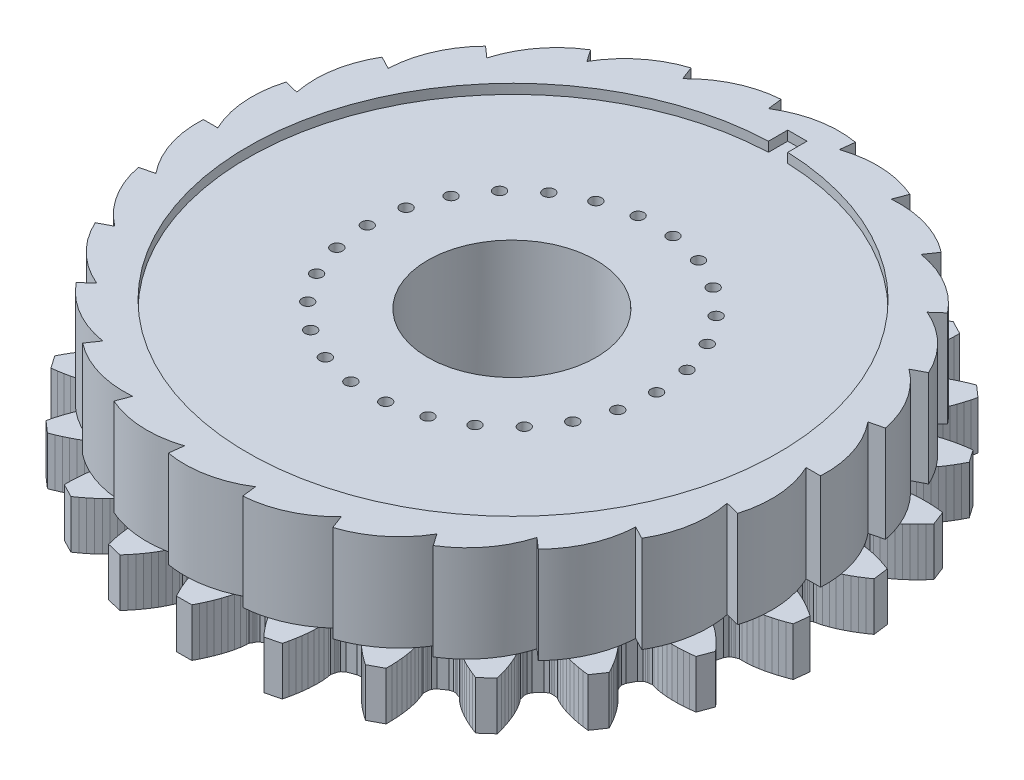
SolidWorks part; units mm, degrees
material "1060 Alloy"
ref_plane "Front Plane" through (0, 0, 0) normal (0, 0, 1) x (1, 0, 0)
ref_plane "Top Plane" through (0, 0, 0) normal (0, 1, 0) x (1, 0, 0)
ref_plane "Right Plane" through (0, 0, 0) normal (1, 0, 0) x (0, 0, -1)
sketch "Sketch1" plane through (0, 0, 0) normal (0, 1, 0) x (1, 0, 0)
  line L0 (0, 0) -> (54.8903, 0) construction
  line L1 (0, 0) -> (47.5263, 11.7142) construction
  line L2 (0, 0) -> (29.6137, 7.2991)
  line L3 (0, 0) -> (32, 0)
  circle A0 centre (0, 0) radius 32 construction
  circle A1 centre (0, 0) radius 30.5 construction
  arc A2 (29.6137, 7.2991) -> (32, 0) centre (21.3514, 0.5583) cw
  circle A3 centre (0, 0) radius 31.25 construction
  dimension "D1" = 62.5
  dimension "D2" = 1.5
  dimension "D4" = 0.75
  dimension "D3" = 13.846
extrude "Extrude ratchet edge" add sketch "Sketch1" along normal blind 10
pattern_circular "Pattern edge to form gear" count 26 over 360 about axis through (0, 10, 0) along (0, -1, 0) of "Extrude ratchet edge" reverse direction yes
sketch "Sketch7" plane through (0, 10, 0) normal (0, 1, 0) x (1, 0, 0)
  circle A0 centre (0, 0) radius 8.7313
  dimension "D1" = 17.4625
sketch "Sketch12" plane through (0, 0, 0) normal (0, -1, 0) x (1, 0, 0)
  line L0 (29.0003, -0.6166) -> (29.1196, -1.0003)
  line L1 (29.1196, -1.0003) -> (29.244, -1.1506)
  line L2 (29.244, -1.1506) -> (29.3694, -1.2597)
  line L3 (29.3694, -1.2597) -> (29.4955, -1.346)
  line L4 (29.4955, -1.346) -> (29.7463, -1.5351)
  line L5 (29.7463, -1.5351) -> (30.0039, -1.5796)
  line L6 (30.0039, -1.5796) -> (30.5166, -1.7122)
  line L7 (30.5166, -1.7122) -> (31.0266, -1.8861)
  line L8 (31.0266, -1.8861) -> (31.5336, -2.0936)
  line L9 (31.5336, -2.0936) -> (32.0376, -2.3308)
  line L10 (32.0376, -2.3308) -> (32.5381, -2.595)
  line L11 (32.5381, -2.595) -> (33.035, -2.8848)
  line L12 (33.035, -2.8848) -> (33.5277, -3.1987)
  line L13 (33.5277, -3.1987) -> (34.0159, -3.5359)
  line L14 (34.0159, -3.5359) -> (33.8164, -5.1042)
  line L15 (33.8164, -5.1042) -> (33.2594, -5.3084)
  line L16 (33.2594, -5.3084) -> (32.7038, -5.4891)
  line L17 (32.7038, -5.4891) -> (32.1503, -5.6453)
  line L18 (32.1503, -5.6453) -> (31.5995, -5.7759)
  line L19 (31.5995, -5.7759) -> (31.0523, -5.8793)
  line L20 (31.0523, -5.8793) -> (30.5094, -5.9534)
  line L21 (30.5094, -5.9534) -> (29.9722, -5.9942)
  line L22 (29.9722, -5.9942) -> (29.4426, -5.9942)
  line L23 (29.4426, -5.9942) -> (29.182, -5.9728)
  line L24 (29.182, -5.9728) -> (28.8919, -6.0931)
  line L25 (28.8919, -6.0931) -> (28.7482, -6.1452)
  line L26 (28.7482, -6.1452) -> (28.5995, -6.2194)
  line L27 (28.5995, -6.2194) -> (28.4414, -6.3338)
  line L28 (28.4414, -6.3338) -> (28.2299, -6.6755)
  line L29 (28.2299, -6.6755) -> (28.0119, -7.539)
  line L30 (28.0119, -7.539) -> (28.0359, -7.9401)
  line L31 (28.0359, -7.9401) -> (28.1207, -8.1159)
  line L32 (28.1207, -8.1159) -> (28.2164, -8.2517)
  line L33 (28.2164, -8.2517) -> (28.3182, -8.3658)
  line L34 (28.3182, -8.3658) -> (28.5164, -8.6094)
  line L35 (28.5164, -8.6094) -> (28.7559, -8.7142)
  line L36 (28.7559, -8.7142) -> (29.222, -8.9657)
  line L37 (29.222, -8.9657) -> (29.6755, -9.2566)
  line L38 (29.6755, -9.2566) -> (30.1181, -9.5794)
  line L39 (30.1181, -9.5794) -> (30.5507, -9.9303)
  line L40 (30.5507, -9.9303) -> (30.9735, -10.3067)
  line L41 (30.9735, -10.3067) -> (31.3865, -10.7069)
  line L42 (31.3865, -10.7069) -> (31.7898, -11.1296)
  line L43 (31.7898, -11.1296) -> (32.1831, -11.5738)
  line L44 (32.1831, -11.5738) -> (31.6141, -13.0488)
  line L45 (31.6141, -13.0488) -> (31.0244, -13.1138)
  line L46 (31.0244, -13.1138) -> (30.4418, -13.1563)
  line L47 (30.4418, -13.1563) -> (29.8669, -13.1754)
  line L48 (29.8669, -13.1754) -> (29.3009, -13.1704)
  line L49 (29.3009, -13.1704) -> (28.7448, -13.1399)
  line L50 (28.7448, -13.1399) -> (28.2, -13.0819)
  line L51 (28.2, -13.0819) -> (27.6686, -12.9929)
  line L52 (27.6686, -12.9929) -> (27.1544, -12.8663)
  line L53 (27.1544, -12.8663) -> (26.9065, -12.7831)
  line L54 (26.9065, -12.7831) -> (26.5961, -12.8305)
  line L55 (26.5961, -12.8305) -> (26.4441, -12.8467)
  line L56 (26.4441, -12.8467) -> (26.2819, -12.8831)
  line L57 (26.2819, -12.8831) -> (26.1011, -12.9564)
  line L58 (26.1011, -12.9564) -> (25.814, -13.2375)
  line L59 (25.814, -13.2375) -> (25.3956, -14.0238)
  line L60 (25.3956, -14.0238) -> (25.3229, -14.4189)
  line L61 (25.3229, -14.4189) -> (25.3632, -14.6099)
  line L62 (25.3632, -14.6099) -> (25.4236, -14.7647)
  line L63 (25.4236, -14.7647) -> (25.4951, -14.8998)
  line L64 (25.4951, -14.8998) -> (25.6292, -15.1838)
  line L65 (25.6292, -15.1838) -> (25.8367, -15.3428)
  line L66 (25.8367, -15.3428) -> (26.2291, -15.6985)
  line L67 (26.2291, -15.6985) -> (26.5998, -16.0895)
  line L68 (26.5998, -16.0895) -> (26.9523, -16.5089)
  line L69 (26.9523, -16.5089) -> (27.2883, -16.9531)
  line L70 (27.2883, -16.9531) -> (27.6087, -17.4197)
  line L71 (27.6087, -17.4197) -> (27.914, -17.9072)
  line L72 (27.914, -17.9072) -> (28.2044, -18.4141)
  line L73 (28.2044, -18.4141) -> (28.48, -18.9395)
  line L74 (28.48, -18.9395) -> (27.5746, -20.2355)
  line L75 (27.5746, -20.2355) -> (26.9864, -20.1575)
  line L76 (26.9864, -20.1575) -> (26.4105, -20.0593)
  line L77 (26.4105, -20.0593) -> (25.8478, -19.9403)
  line L78 (25.8478, -19.9403) -> (25.2994, -19.8)
  line L79 (25.2994, -19.8) -> (24.7668, -19.6373)
  line L80 (24.7668, -19.6373) -> (24.2517, -19.4506)
  line L81 (24.2517, -19.4506) -> (23.7571, -19.237)
  line L82 (23.7571, -19.237) -> (23.2881, -18.991)
  line L83 (23.2881, -18.991) -> (23.0673, -18.8509)
  line L84 (23.0673, -18.8509) -> (22.7546, -18.8226)
  line L85 (22.7546, -18.8226) -> (22.6031, -18.802)
  line L86 (22.6031, -18.802) -> (22.4369, -18.7985)
  line L87 (22.4369, -18.7985) -> (22.2438, -18.8264)
  line L88 (22.2438, -18.8264) -> (21.8978, -19.0306)
  line L89 (21.8978, -19.0306) -> (21.3034, -19.694)
  line L90 (21.3034, -19.694) -> (21.1383, -20.0602)
  line L91 (21.1383, -20.0602) -> (21.1316, -20.2553)
  line L92 (21.1316, -20.2553) -> (21.1532, -20.4201)
  line L93 (21.1532, -20.4201) -> (21.1903, -20.5684)
  line L94 (21.1903, -20.5684) -> (21.2526, -20.8761)
  line L95 (21.2526, -20.8761) -> (21.416, -21.0803)
  line L96 (21.416, -21.0803) -> (21.7119, -21.5195)
  line L97 (21.7119, -21.5195) -> (21.9782, -21.9879)
  line L98 (21.9782, -21.9879) -> (22.2201, -22.4794)
  line L99 (22.2201, -22.4794) -> (22.4401, -22.9911)
  line L100 (22.4401, -22.9911) -> (22.6395, -23.5209)
  line L101 (22.6395, -23.5209) -> (22.8193, -24.0672)
  line L102 (22.8193, -24.0672) -> (22.9799, -24.6289)
  line L103 (22.9799, -24.6289) -> (23.1217, -25.205)
  line L104 (23.1217, -25.205) -> (21.9325, -26.2467)
  line L105 (21.9325, -26.2467) -> (21.3801, -26.0302)
  line L106 (21.3801, -26.0302) -> (20.8445, -25.797)
  line L107 (20.8445, -25.797) -> (20.3266, -25.5468)
  line L108 (20.3266, -25.5468) -> (19.8277, -25.2793)
  line L109 (19.8277, -25.2793) -> (19.3494, -24.9939)
  line L110 (19.3494, -24.9939) -> (18.894, -24.6893)
  line L111 (18.894, -24.6893) -> (18.4649, -24.3636)
  line L112 (18.4649, -24.3636) -> (18.0684, -24.0125)
  line L113 (18.0684, -24.0125) -> (17.8876, -23.8237)
  line L114 (17.8876, -23.8237) -> (17.5907, -23.7213)
  line L115 (17.5907, -23.7213) -> (17.4485, -23.665)
  line L116 (17.4485, -23.665) -> (17.288, -23.6219)
  line L117 (17.288, -23.6219) -> (17.0938, -23.6028)
  line L118 (17.0938, -23.6028) -> (16.709, -23.7182)
  line L119 (16.709, -23.7182) -> (15.9732, -24.22)
  line L120 (15.9732, -24.22) -> (15.7251, -24.5362)
  line L121 (15.7251, -24.5362) -> (15.672, -24.7239)
  line L122 (15.672, -24.7239) -> (15.6536, -24.8891)
  line L123 (15.6536, -24.8891) -> (15.6541, -25.042)
  line L124 (15.6541, -25.042) -> (15.641, -25.3558)
  line L125 (15.641, -25.3558) -> (15.7507, -25.593)
  line L126 (15.7507, -25.593) -> (15.9329, -26.0903)
  line L127 (15.9329, -26.0903) -> (16.0794, -26.6088)
  line L128 (16.0794, -26.6088) -> (16.1966, -27.144)
  line L129 (16.1966, -27.144) -> (16.2878, -27.6934)
  line L130 (16.2878, -27.6934) -> (16.3546, -28.2555)
  line L131 (16.3546, -28.2555) -> (16.3984, -28.829)
  line L132 (16.3984, -28.829) -> (16.4199, -29.4128)
  line L133 (16.4199, -29.4128) -> (16.4198, -30.0061)
  line L134 (16.4198, -30.0061) -> (15.0158, -30.7329)
  line L135 (15.0158, -30.7329) -> (14.5313, -30.3905)
  line L136 (14.5313, -30.3905) -> (14.067, -30.0359)
  line L137 (14.067, -30.0359) -> (13.624, -29.6691)
  line L138 (13.624, -29.6691) -> (13.2037, -29.29)
  line L139 (13.2037, -29.29) -> (12.8076, -28.8984)
  line L140 (12.8076, -28.8984) -> (12.4383, -28.4937)
  line L141 (12.4383, -28.4937) -> (12.0996, -28.0747)
  line L142 (12.0996, -28.0747) -> (11.7986, -27.6389)
  line L143 (11.7986, -27.6389) -> (11.6683, -27.4123)
  line L144 (11.6683, -27.4123) -> (11.4045, -27.2419)
  line L145 (11.4045, -27.2419) -> (11.28, -27.1532)
  line L146 (11.28, -27.1532) -> (11.1345, -27.0729)
  line L147 (11.1345, -27.0729) -> (10.9505, -27.0079)
  line L148 (10.9505, -27.0079) -> (10.5492, -27.0279)
  line L149 (10.5492, -27.0279) -> (9.7146, -27.339)
  line L150 (9.7146, -27.339) -> (9.3982, -27.5866)
  line L151 (9.3982, -27.5866) -> (9.3017, -27.7562)
  line L152 (9.3017, -27.7562) -> (9.2442, -27.9122)
  line L153 (9.2442, -27.9122) -> (9.2082, -28.0607)
  line L154 (9.2082, -28.0607) -> (9.1203, -28.3622)
  line L155 (9.1203, -28.3622) -> (9.1701, -28.6189)
  line L156 (9.1701, -28.6189) -> (9.2279, -29.1453)
  line L157 (9.2279, -29.1453) -> (9.2461, -29.6838)
  line L158 (9.2461, -29.6838) -> (9.2319, -30.2315)
  line L159 (9.2319, -30.2315) -> (9.1888, -30.7868)
  line L160 (9.1888, -30.7868) -> (9.1192, -31.3485)
  line L161 (9.1192, -31.3485) -> (9.0245, -31.9158)
  line L162 (9.0245, -31.9158) -> (8.9057, -32.4878)
  line L163 (8.9057, -32.4878) -> (8.7636, -33.0638)
  line L164 (8.7636, -33.0638) -> (7.2264, -33.4335)
  line L165 (7.2264, -33.4335) -> (6.8379, -32.9851)
  line L166 (6.8379, -32.9851) -> (6.472, -32.5297)
  line L167 (6.472, -32.5297) -> (6.1297, -32.0675)
  line L168 (6.1297, -32.0675) -> (5.8123, -31.5988)
  line L169 (5.8123, -31.5988) -> (5.5215, -31.1238)
  line L170 (5.5215, -31.1238) -> (5.2598, -30.6425)
  line L171 (5.2598, -30.6425) -> (5.0311, -30.1547)
  line L172 (5.0311, -30.1547) -> (4.8432, -29.6595)
  line L173 (4.8432, -29.6595) -> (4.7709, -29.4083)
  line L174 (4.7709, -29.4083) -> (4.5555, -29.1797)
  line L175 (4.5555, -29.1797) -> (4.4559, -29.0638)
  line L176 (4.4559, -29.0638) -> (4.3338, -28.951)
  line L177 (4.3338, -28.951) -> (4.1707, -28.8438)
  line L178 (4.1707, -28.8438) -> (3.7763, -28.7672)
  line L179 (3.7763, -28.7672) -> (2.8915, -28.8696)
  line L180 (2.8915, -28.8696) -> (2.525, -29.0342)
  line L181 (2.525, -29.0342) -> (2.3907, -29.1758)
  line L182 (2.3907, -29.1758) -> (2.2976, -29.3135)
  line L183 (2.2976, -29.3135) -> (2.2271, -29.4491)
  line L184 (2.2271, -29.4491) -> (2.0696, -29.7208)
  line L185 (2.0696, -29.7208) -> (2.0565, -29.9819)
  line L186 (2.0565, -29.9819) -> (1.9867, -30.5069)
  line L187 (1.9867, -30.5069) -> (1.8755, -31.0341)
  line L188 (1.8755, -31.0341) -> (1.7306, -31.5624)
  line L189 (1.7306, -31.5624) -> (1.5559, -32.0913)
  line L190 (1.5559, -32.0913) -> (1.3539, -32.6201)
  line L191 (1.3539, -32.6201) -> (1.1262, -33.1482)
  line L192 (1.1262, -33.1482) -> (0.8739, -33.6752)
  line L193 (0.8739, -33.6752) -> (0.5981, -34.2004)
  line L194 (0.5981, -34.2004) -> (-0.9829, -34.1915)
  line L195 (-0.9829, -34.1915) -> (-1.2528, -33.6632)
  line L196 (-1.2528, -33.6632) -> (-1.499, -33.1334)
  line L197 (-1.499, -33.1334) -> (-1.7208, -32.6027)
  line L198 (-1.7208, -32.6027) -> (-1.9169, -32.0717)
  line L199 (-1.9169, -32.0717) -> (-2.0855, -31.5409)
  line L200 (-2.0855, -31.5409) -> (-2.2244, -31.011)
  line L201 (-2.2244, -31.011) -> (-2.3297, -30.4826)
  line L202 (-2.3297, -30.4826) -> (-2.3936, -29.9568)
  line L203 (-2.3936, -29.9568) -> (-2.4037, -29.6956)
  line L204 (-2.4037, -29.6956) -> (-2.5581, -29.4221)
  line L205 (-2.5581, -29.4221) -> (-2.6272, -29.2857)
  line L206 (-2.6272, -29.2857) -> (-2.7187, -29.147)
  line L207 (-2.7187, -29.147) -> (-2.8514, -29.0039)
  line L208 (-2.8514, -29.0039) -> (-3.216, -28.8351)
  line L209 (-3.216, -28.8351) -> (-4.0996, -28.7228)
  line L210 (-4.0996, -28.7228) -> (-4.4948, -28.7949)
  line L211 (-4.4948, -28.7949) -> (-4.6591, -28.9003)
  line L212 (-4.6591, -28.9003) -> (-4.7824, -29.0117)
  line L213 (-4.7824, -29.0117) -> (-4.8834, -29.1265)
  line L214 (-4.8834, -29.1265) -> (-5.1013, -29.3526)
  line L215 (-5.1013, -29.3526) -> (-5.1765, -29.603)
  line L216 (-5.1765, -29.603) -> (-5.37, -30.096)
  line L217 (-5.37, -30.096) -> (-5.6041, -30.5812)
  line L218 (-5.6041, -30.5812) -> (-5.8712, -31.0596)
  line L219 (-5.8712, -31.0596) -> (-6.1674, -31.5313)
  line L220 (-6.1674, -31.5313) -> (-6.4901, -31.9963)
  line L221 (-6.4901, -31.9963) -> (-6.8376, -32.4546)
  line L222 (-6.8376, -32.4546) -> (-7.2086, -32.9059)
  line L223 (-7.2086, -32.9059) -> (-7.6021, -33.3499)
  line L224 (-7.6021, -33.3499) -> (-9.135, -32.9629)
  line L225 (-9.135, -32.9629) -> (-9.2706, -32.3853)
  line L226 (-9.2706, -32.3853) -> (-9.383, -31.812)
  line L227 (-9.383, -31.812) -> (-9.4713, -31.2437)
  line L228 (-9.4713, -31.2437) -> (-9.5346, -30.6812)
  line L229 (-9.5346, -30.6812) -> (-9.5713, -30.1254)
  line L230 (-9.5713, -30.1254) -> (-9.5793, -29.5776)
  line L231 (-9.5793, -29.5776) -> (-9.5551, -29.0394)
  line L232 (-9.5551, -29.0394) -> (-9.4913, -28.5136)
  line L233 (-9.4913, -28.5136) -> (-9.4387, -28.2576)
  line L234 (-9.4387, -28.2576) -> (-9.5231, -27.9551)
  line L235 (-9.5231, -27.9551) -> (-9.5575, -27.8061)
  line L236 (-9.5575, -27.8061) -> (-9.6132, -27.6496)
  line L237 (-9.6132, -27.6496) -> (-9.7078, -27.4789)
  line L238 (-9.7078, -27.4789) -> (-10.0214, -27.2277)
  line L239 (-10.0214, -27.2277) -> (-10.8524, -26.9072)
  line L240 (-10.8524, -26.9072) -> (-11.2535, -26.8827)
  line L241 (-11.2535, -26.8827) -> (-11.4382, -26.9456)
  line L242 (-11.4382, -26.9456) -> (-11.5846, -27.0243)
  line L243 (-11.5846, -27.0243) -> (-11.7101, -27.1116)
  line L244 (-11.7101, -27.1116) -> (-11.9758, -27.279)
  line L245 (-11.9758, -27.279) -> (-12.1087, -27.5041)
  line L246 (-12.1087, -27.5041) -> (-12.4145, -27.9365)
  line L247 (-12.4145, -27.9365) -> (-12.758, -28.3516)
  line L248 (-12.758, -28.3516) -> (-13.1318, -28.7521)
  line L249 (-13.1318, -28.7521) -> (-13.5322, -29.1392)
  line L250 (-13.5322, -29.1392) -> (-13.9568, -29.5135)
  line L251 (-13.9568, -29.5135) -> (-14.4039, -29.8753)
  line L252 (-14.4039, -29.8753) -> (-14.8722, -30.2247)
  line L253 (-14.8722, -30.2247) -> (-15.3605, -30.5616)
  line L254 (-15.3605, -30.5616) -> (-16.7562, -29.819)
  line L255 (-16.7562, -29.819) -> (-16.7497, -29.2258)
  line L256 (-16.7497, -29.2258) -> (-16.7216, -28.6422)
  line L257 (-16.7216, -28.6422) -> (-16.6713, -28.0693)
  line L258 (-16.6713, -28.0693) -> (-16.5981, -27.508)
  line L259 (-16.5981, -27.508) -> (-16.5008, -26.9596)
  line L260 (-16.5008, -26.9596) -> (-16.3775, -26.4258)
  line L261 (-16.3775, -26.4258) -> (-16.2252, -25.909)
  line L262 (-16.2252, -25.909) -> (-16.0374, -25.4138)
  line L263 (-16.0374, -25.4138) -> (-15.925, -25.1778)
  line L264 (-15.925, -25.1778) -> (-15.9346, -24.8639)
  line L265 (-15.9346, -24.8639) -> (-15.9324, -24.711)
  line L266 (-15.9324, -24.711) -> (-15.949, -24.5456)
  line L267 (-15.949, -24.5456) -> (-15.9999, -24.3573)
  line L268 (-15.9999, -24.3573) -> (-16.2444, -24.0384)
  line L269 (-16.2444, -24.0384) -> (-16.9745, -23.5283)
  line L270 (-16.9745, -23.5283) -> (-17.358, -23.4085)
  line L271 (-17.358, -23.4085) -> (-17.5524, -23.4254)
  line L272 (-17.5524, -23.4254) -> (-17.7134, -23.4668)
  line L273 (-17.7134, -23.4668) -> (-17.8562, -23.5215)
  line L274 (-17.8562, -23.5215) -> (-18.1542, -23.6204)
  line L275 (-18.1542, -23.6204) -> (-18.3371, -23.8072)
  line L276 (-18.3371, -23.8072) -> (-18.7375, -24.1538)
  line L277 (-18.7375, -24.1538) -> (-19.1704, -24.4747)
  line L278 (-19.1704, -24.4747) -> (-19.6292, -24.7741)
  line L279 (-19.6292, -24.7741) -> (-20.1106, -25.0541)
  line L280 (-20.1106, -25.0541) -> (-20.6125, -25.316)
  line L281 (-20.6125, -25.316) -> (-21.1332, -25.5603)
  line L282 (-21.1332, -25.5603) -> (-21.6714, -25.7874)
  line L283 (-21.6714, -25.7874) -> (-22.2262, -25.9977)
  line L284 (-22.2262, -25.9977) -> (-23.4036, -24.9426)
  line L285 (-23.4036, -24.9426) -> (-23.2553, -24.3682)
  line L286 (-23.2553, -24.3682) -> (-23.0883, -23.8083)
  line L287 (-23.0883, -23.8083) -> (-22.9024, -23.2641)
  line L288 (-22.9024, -23.2641) -> (-22.6971, -22.7366)
  line L289 (-22.6971, -22.7366) -> (-22.4713, -22.2274)
  line L290 (-22.4713, -22.2274) -> (-22.2239, -21.7386)
  line L291 (-22.2239, -21.7386) -> (-21.9523, -21.2733)
  line L292 (-21.9523, -21.2733) -> (-21.6515, -20.8374)
  line L293 (-21.6515, -20.8374) -> (-21.4858, -20.6352)
  line L294 (-21.4858, -20.6352) -> (-21.4201, -20.3281)
  line L295 (-21.4201, -20.3281) -> (-21.3813, -20.1802)
  line L296 (-21.3813, -20.1802) -> (-21.3578, -20.0157)
  line L297 (-21.3578, -20.0157) -> (-21.3622, -19.8206)
  line L298 (-21.3622, -19.8206) -> (-21.5232, -19.4525)
  line L299 (-21.5232, -19.4525) -> (-22.1101, -18.7825)
  line L300 (-22.1101, -18.7825) -> (-22.4538, -18.5744)
  line L301 (-22.4538, -18.5744) -> (-22.6466, -18.5443)
  line L302 (-22.6466, -18.5443) -> (-22.8128, -18.5459)
  line L303 (-22.8128, -18.5459) -> (-22.9645, -18.5648)
  line L304 (-22.9645, -18.5648) -> (-23.2775, -18.5896)
  line L305 (-23.2775, -18.5896) -> (-23.4999, -18.7272)
  line L306 (-23.4999, -18.7272) -> (-23.9716, -18.9679)
  line L307 (-23.9716, -18.9679) -> (-24.4686, -19.1758)
  line L308 (-24.4686, -19.1758) -> (-24.9858, -19.3568)
  line L309 (-24.9858, -19.3568) -> (-25.5202, -19.5135)
  line L310 (-25.5202, -19.5135) -> (-26.0702, -19.6476)
  line L311 (-26.0702, -19.6476) -> (-26.6342, -19.7602)
  line L312 (-26.6342, -19.7602) -> (-27.2111, -19.8519)
  line L313 (-27.2111, -19.8519) -> (-27.8001, -19.9233)
  line L314 (-27.8001, -19.9233) -> (-28.6909, -18.6171)
  line L315 (-28.6909, -18.6171) -> (-28.4094, -18.0949)
  line L316 (-28.4094, -18.0949) -> (-28.1133, -17.5912)
  line L317 (-28.1133, -17.5912) -> (-27.8025, -17.1073)
  line L318 (-27.8025, -17.1073) -> (-27.4769, -16.6443)
  line L319 (-27.4769, -16.6443) -> (-27.1359, -16.2039)
  line L320 (-27.1359, -16.2039) -> (-26.7786, -15.7885)
  line L321 (-26.7786, -15.7885) -> (-26.4036, -15.4018)
  line L322 (-26.4036, -15.4018) -> (-26.0072, -15.0505)
  line L323 (-26.0072, -15.0505) -> (-25.7979, -14.8938)
  line L324 (-25.7979, -14.8938) -> (-25.6606, -14.6114)
  line L325 (-25.6606, -14.6114) -> (-25.5876, -14.4771)
  line L326 (-25.5876, -14.4771) -> (-25.5254, -14.3229)
  line L327 (-25.5254, -14.3229) -> (-25.483, -14.1325)
  line L328 (-25.483, -14.1325) -> (-25.5512, -13.7365)
  line L329 (-25.5512, -13.7365) -> (-25.9607, -12.9455)
  line L330 (-25.9607, -12.9455) -> (-26.2446, -12.6612)
  line L331 (-26.2446, -12.6612) -> (-26.4246, -12.5859)
  line L332 (-26.4246, -12.5859) -> (-26.5864, -12.5476)
  line L333 (-26.5864, -12.5476) -> (-26.7382, -12.5297)
  line L334 (-26.7382, -12.5297) -> (-27.0481, -12.4789)
  line L335 (-27.0481, -12.4789) -> (-27.2968, -12.5592)
  line L336 (-27.2968, -12.5592) -> (-27.8125, -12.6801)
  line L337 (-27.8125, -12.6801) -> (-28.3448, -12.763)
  line L338 (-28.3448, -12.763) -> (-28.8902, -12.8149)
  line L339 (-28.8902, -12.8149) -> (-29.4467, -12.8392)
  line L340 (-29.4467, -12.8392) -> (-30.0127, -12.8378)
  line L341 (-30.0127, -12.8378) -> (-30.5873, -12.8121)
  line L342 (-30.5873, -12.8121) -> (-31.1694, -12.7631)
  line L343 (-31.1694, -12.7631) -> (-31.7584, -12.6915)
  line L344 (-31.7584, -12.6915) -> (-32.3107, -11.2101)
  line L345 (-32.3107, -11.2101) -> (-31.9124, -10.7704)
  line L346 (-31.9124, -10.7704) -> (-31.5044, -10.3522)
  line L347 (-31.5044, -10.3522) -> (-31.0868, -9.9567)
  line L348 (-31.0868, -9.9567) -> (-30.6598, -9.5851)
  line L349 (-30.6598, -9.5851) -> (-30.2233, -9.2392)
  line L350 (-30.2233, -9.2392) -> (-29.7771, -8.9214)
  line L351 (-29.7771, -8.9214) -> (-29.3203, -8.6356)
  line L352 (-29.3203, -8.6356) -> (-28.8514, -8.3894)
  line L353 (-28.8514, -8.3894) -> (-28.6108, -8.2873)
  line L354 (-28.6108, -8.2873) -> (-28.4098, -8.0459)
  line L355 (-28.4098, -8.0459) -> (-28.3068, -7.933)
  line L356 (-28.3068, -7.933) -> (-28.2095, -7.7982)
  line L357 (-28.2095, -7.7982) -> (-28.1228, -7.6234)
  line L358 (-28.1228, -7.6234) -> (-28.0943, -7.2226)
  line L359 (-28.0943, -7.2226) -> (-28.3025, -6.3567)
  line L360 (-28.3025, -6.3567) -> (-28.5102, -6.0127)
  line L361 (-28.5102, -6.0127) -> (-28.6669, -5.8964)
  line L362 (-28.6669, -5.8964) -> (-28.8148, -5.8206)
  line L363 (-28.8148, -5.8206) -> (-28.9579, -5.7669)
  line L364 (-28.9579, -5.7669) -> (-29.2466, -5.6433)
  line L365 (-29.2466, -5.6433) -> (-29.5074, -5.6618)
  line L366 (-29.5074, -5.6618) -> (-30.037, -5.6558)
  line L367 (-30.037, -5.6558) -> (-30.5737, -5.6089)
  line L368 (-30.5737, -5.6089) -> (-31.1157, -5.5288)
  line L369 (-31.1157, -5.5288) -> (-31.6618, -5.4192)
  line L370 (-31.6618, -5.4192) -> (-32.211, -5.2824)
  line L371 (-32.211, -5.2824) -> (-32.7628, -5.1199)
  line L372 (-32.7628, -5.1199) -> (-33.3163, -4.933)
  line L373 (-33.3163, -4.933) -> (-33.871, -4.7225)
  line L374 (-33.871, -4.7225) -> (-34.0527, -3.152)
  line L375 (-34.0527, -3.152) -> (-33.5607, -2.8204)
  line L376 (-33.5607, -2.8204) -> (-33.0645, -2.5121)
  line L377 (-33.0645, -2.5121) -> (-32.5644, -2.228)
  line L378 (-32.5644, -2.228) -> (-32.0609, -1.9693)
  line L379 (-32.0609, -1.9693) -> (-31.5543, -1.7379)
  line L380 (-31.5543, -1.7379) -> (-31.045, -1.5361)
  line L381 (-31.045, -1.5361) -> (-30.5331, -1.3679)
  line L382 (-30.5331, -1.3679) -> (-30.0189, -1.2411)
  line L383 (-30.0189, -1.2411) -> (-29.7608, -1.1996)
  line L384 (-29.7608, -1.1996) -> (-29.5079, -1.0133)
  line L385 (-29.5079, -1.0133) -> (-29.3809, -0.9284)
  line L386 (-29.3809, -0.9284) -> (-29.2542, -0.8208)
  line L387 (-29.2542, -0.8208) -> (-29.1281, -0.6718)
  line L388 (-29.1281, -0.6718) -> (-29.0045, -0.2895)
  line L389 (-29.0045, -0.2895) -> (-28.9995, 0.6011)
  line L390 (-28.9995, 0.6011) -> (-29.1188, 0.9848)
  line L391 (-29.1188, 0.9848) -> (-29.2432, 1.1352)
  line L392 (-29.2432, 1.1352) -> (-29.3686, 1.2442)
  line L393 (-29.3686, 1.2442) -> (-29.4947, 1.3306)
  line L394 (-29.4947, 1.3306) -> (-29.7455, 1.5197)
  line L395 (-29.7455, 1.5197) -> (-30.0031, 1.5641)
  line L396 (-30.0031, 1.5641) -> (-30.5158, 1.6968)
  line L397 (-30.5158, 1.6968) -> (-31.0257, 1.8707)
  line L398 (-31.0257, 1.8707) -> (-31.5328, 2.0782)
  line L399 (-31.5328, 2.0782) -> (-32.0368, 2.3153)
  line L400 (-32.0368, 2.3153) -> (-32.5373, 2.5796)
  line L401 (-32.5373, 2.5796) -> (-33.0342, 2.8694)
  line L402 (-33.0342, 2.8694) -> (-33.5269, 3.1833)
  line L403 (-33.5269, 3.1833) -> (-34.0151, 3.5204)
  line L404 (-34.0151, 3.5204) -> (-33.8156, 5.0888)
  line L405 (-33.8156, 5.0888) -> (-33.2586, 5.293)
  line L406 (-33.2586, 5.293) -> (-32.703, 5.4737)
  line L407 (-32.703, 5.4737) -> (-32.1495, 5.6298)
  line L408 (-32.1495, 5.6298) -> (-31.5987, 5.7604)
  line L409 (-31.5987, 5.7604) -> (-31.0515, 5.8639)
  line L410 (-31.0515, 5.8639) -> (-30.5086, 5.9379)
  line L411 (-30.5086, 5.9379) -> (-29.9714, 5.9787)
  line L412 (-29.9714, 5.9787) -> (-29.4418, 5.9788)
  line L413 (-29.4418, 5.9788) -> (-29.1812, 5.9574)
  line L414 (-29.1812, 5.9574) -> (-28.8911, 6.0777)
  line L415 (-28.8911, 6.0777) -> (-28.7474, 6.1298)
  line L416 (-28.7474, 6.1298) -> (-28.5987, 6.2039)
  line L417 (-28.5987, 6.2039) -> (-28.4406, 6.3184)
  line L418 (-28.4406, 6.3184) -> (-28.2291, 6.66)
  line L419 (-28.2291, 6.66) -> (-28.0111, 7.5236)
  line L420 (-28.0111, 7.5236) -> (-28.0351, 7.9247)
  line L421 (-28.0351, 7.9247) -> (-28.1199, 8.1004)
  line L422 (-28.1199, 8.1004) -> (-28.2156, 8.2363)
  line L423 (-28.2156, 8.2363) -> (-28.3174, 8.3504)
  line L424 (-28.3174, 8.3504) -> (-28.5156, 8.594)
  line L425 (-28.5156, 8.594) -> (-28.7551, 8.6988)
  line L426 (-28.7551, 8.6988) -> (-29.2212, 8.9502)
  line L427 (-29.2212, 8.9502) -> (-29.6746, 9.2412)
  line L428 (-29.6746, 9.2412) -> (-30.1173, 9.564)
  line L429 (-30.1173, 9.564) -> (-30.5499, 9.9148)
  line L430 (-30.5499, 9.9148) -> (-30.9727, 10.2912)
  line L431 (-30.9727, 10.2912) -> (-31.3857, 10.6914)
  line L432 (-31.3857, 10.6914) -> (-31.789, 11.1142)
  line L433 (-31.789, 11.1142) -> (-32.1823, 11.5583)
  line L434 (-32.1823, 11.5583) -> (-31.6133, 13.0334)
  line L435 (-31.6133, 13.0334) -> (-31.0236, 13.0984)
  line L436 (-31.0236, 13.0984) -> (-30.4409, 13.1408)
  line L437 (-30.4409, 13.1408) -> (-29.8661, 13.16)
  line L438 (-29.8661, 13.16) -> (-29.3001, 13.155)
  line L439 (-29.3001, 13.155) -> (-28.744, 13.1245)
  line L440 (-28.744, 13.1245) -> (-28.1992, 13.0665)
  line L441 (-28.1992, 13.0665) -> (-27.6678, 12.9775)
  line L442 (-27.6678, 12.9775) -> (-27.1536, 12.8508)
  line L443 (-27.1536, 12.8508) -> (-26.9057, 12.7677)
  line L444 (-26.9057, 12.7677) -> (-26.5953, 12.8151)
  line L445 (-26.5953, 12.8151) -> (-26.4433, 12.8312)
  line L446 (-26.4433, 12.8312) -> (-26.2811, 12.8676)
  line L447 (-26.2811, 12.8676) -> (-26.1002, 12.941)
  line L448 (-26.1002, 12.941) -> (-25.8131, 13.222)
  line L449 (-25.8131, 13.222) -> (-25.3948, 14.0083)
  line L450 (-25.3948, 14.0083) -> (-25.3221, 14.4035)
  line L451 (-25.3221, 14.4035) -> (-25.3623, 14.5945)
  line L452 (-25.3623, 14.5945) -> (-25.4228, 14.7493)
  line L453 (-25.4228, 14.7493) -> (-25.4943, 14.8844)
  line L454 (-25.4943, 14.8844) -> (-25.6284, 15.1683)
  line L455 (-25.6284, 15.1683) -> (-25.8359, 15.3274)
  line L456 (-25.8359, 15.3274) -> (-26.2283, 15.6831)
  line L457 (-26.2283, 15.6831) -> (-26.5989, 16.0741)
  line L458 (-26.5989, 16.0741) -> (-26.9515, 16.4935)
  line L459 (-26.9515, 16.4935) -> (-27.2875, 16.9377)
  line L460 (-27.2875, 16.9377) -> (-27.6079, 17.4043)
  line L461 (-27.6079, 17.4043) -> (-27.9132, 17.8917)
  line L462 (-27.9132, 17.8917) -> (-28.2036, 18.3987)
  line L463 (-28.2036, 18.3987) -> (-28.4792, 18.9241)
  line L464 (-28.4792, 18.9241) -> (-27.5738, 20.2201)
  line L465 (-27.5738, 20.2201) -> (-26.9856, 20.1421)
  line L466 (-26.9856, 20.1421) -> (-26.4097, 20.0438)
  line L467 (-26.4097, 20.0438) -> (-25.847, 19.9249)
  line L468 (-25.847, 19.9249) -> (-25.2986, 19.7846)
  line L469 (-25.2986, 19.7846) -> (-24.766, 19.6219)
  line L470 (-24.766, 19.6219) -> (-24.2509, 19.4351)
  line L471 (-24.2509, 19.4351) -> (-23.7562, 19.2216)
  line L472 (-23.7562, 19.2216) -> (-23.2873, 18.9756)
  line L473 (-23.2873, 18.9756) -> (-23.0665, 18.8355)
  line L474 (-23.0665, 18.8355) -> (-22.7538, 18.8072)
  line L475 (-22.7538, 18.8072) -> (-22.6023, 18.7865)
  line L476 (-22.6023, 18.7865) -> (-22.4361, 18.7831)
  line L477 (-22.4361, 18.7831) -> (-22.243, 18.811)
  line L478 (-22.243, 18.811) -> (-21.897, 19.0152)
  line L479 (-21.897, 19.0152) -> (-21.3026, 19.6785)
  line L480 (-21.3026, 19.6785) -> (-21.1374, 20.0448)
  line L481 (-21.1374, 20.0448) -> (-21.1308, 20.2399)
  line L482 (-21.1308, 20.2399) -> (-21.1524, 20.4046)
  line L483 (-21.1524, 20.4046) -> (-21.1895, 20.5529)
  line L484 (-21.1895, 20.5529) -> (-21.2518, 20.8607)
  line L485 (-21.2518, 20.8607) -> (-21.4152, 21.0648)
  line L486 (-21.4152, 21.0648) -> (-21.7111, 21.5041)
  line L487 (-21.7111, 21.5041) -> (-21.9774, 21.9724)
  line L488 (-21.9774, 21.9724) -> (-22.2193, 22.464)
  line L489 (-22.2193, 22.464) -> (-22.4393, 22.9757)
  line L490 (-22.4393, 22.9757) -> (-22.6387, 23.5054)
  line L491 (-22.6387, 23.5054) -> (-22.8185, 24.0518)
  line L492 (-22.8185, 24.0518) -> (-22.9791, 24.6135)
  line L493 (-22.9791, 24.6135) -> (-23.1209, 25.1896)
  line L494 (-23.1209, 25.1896) -> (-21.9317, 26.2312)
  line L495 (-21.9317, 26.2312) -> (-21.3793, 26.0148)
  line L496 (-21.3793, 26.0148) -> (-20.8436, 25.7815)
  line L497 (-20.8436, 25.7815) -> (-20.3258, 25.5314)
  line L498 (-20.3258, 25.5314) -> (-19.8269, 25.2639)
  line L499 (-19.8269, 25.2639) -> (-19.3486, 24.9785)
  line L500 (-19.3486, 24.9785) -> (-18.8932, 24.6739)
  line L501 (-18.8932, 24.6739) -> (-18.464, 24.3482)
  line L502 (-18.464, 24.3482) -> (-18.0676, 23.997)
  line L503 (-18.0676, 23.997) -> (-17.8868, 23.8082)
  line L504 (-17.8868, 23.8082) -> (-17.5899, 23.7059)
  line L505 (-17.5899, 23.7059) -> (-17.4477, 23.6496)
  line L506 (-17.4477, 23.6496) -> (-17.2872, 23.6065)
  line L507 (-17.2872, 23.6065) -> (-17.093, 23.5873)
  line L508 (-17.093, 23.5873) -> (-16.7082, 23.7028)
  line L509 (-16.7082, 23.7028) -> (-15.9723, 24.2046)
  line L510 (-15.9723, 24.2046) -> (-15.7243, 24.5207)
  line L511 (-15.7243, 24.5207) -> (-15.6712, 24.7085)
  line L512 (-15.6712, 24.7085) -> (-15.6528, 24.8737)
  line L513 (-15.6528, 24.8737) -> (-15.6533, 25.0266)
  line L514 (-15.6533, 25.0266) -> (-15.6401, 25.3403)
  line L515 (-15.6401, 25.3403) -> (-15.7499, 25.5776)
  line L516 (-15.7499, 25.5776) -> (-15.932, 26.0749)
  line L517 (-15.932, 26.0749) -> (-16.0786, 26.5934)
  line L518 (-16.0786, 26.5934) -> (-16.1958, 27.1285)
  line L519 (-16.1958, 27.1285) -> (-16.2869, 27.678)
  line L520 (-16.2869, 27.678) -> (-16.3538, 28.2401)
  line L521 (-16.3538, 28.2401) -> (-16.3976, 28.8136)
  line L522 (-16.3976, 28.8136) -> (-16.4191, 29.3974)
  line L523 (-16.4191, 29.3974) -> (-16.419, 29.9907)
  line L524 (-16.419, 29.9907) -> (-15.015, 30.7175)
  line L525 (-15.015, 30.7175) -> (-14.5305, 30.3751)
  line L526 (-14.5305, 30.3751) -> (-14.0662, 30.0205)
  line L527 (-14.0662, 30.0205) -> (-13.6232, 29.6536)
  line L528 (-13.6232, 29.6536) -> (-13.2028, 29.2746)
  line L529 (-13.2028, 29.2746) -> (-12.8068, 28.8829)
  line L530 (-12.8068, 28.8829) -> (-12.4375, 28.4782)
  line L531 (-12.4375, 28.4782) -> (-12.0988, 28.0593)
  line L532 (-12.0988, 28.0593) -> (-11.7978, 27.6235)
  line L533 (-11.7978, 27.6235) -> (-11.6675, 27.3969)
  line L534 (-11.6675, 27.3969) -> (-11.4037, 27.2265)
  line L535 (-11.4037, 27.2265) -> (-11.2792, 27.1378)
  line L536 (-11.2792, 27.1378) -> (-11.1336, 27.0575)
  line L537 (-11.1336, 27.0575) -> (-10.9497, 26.9924)
  line L538 (-10.9497, 26.9924) -> (-10.5484, 27.0125)
  line L539 (-10.5484, 27.0125) -> (-9.7138, 27.3236)
  line L540 (-9.7138, 27.3236) -> (-9.3974, 27.5712)
  line L541 (-9.3974, 27.5712) -> (-9.3009, 27.7408)
  line L542 (-9.3009, 27.7408) -> (-9.2434, 27.8967)
  line L543 (-9.2434, 27.8967) -> (-9.2073, 28.0453)
  line L544 (-9.2073, 28.0453) -> (-9.1195, 28.3468)
  line L545 (-9.1195, 28.3468) -> (-9.1693, 28.6034)
  line L546 (-9.1693, 28.6034) -> (-9.2271, 29.1299)
  line L547 (-9.2271, 29.1299) -> (-9.2453, 29.6683)
  line L548 (-9.2453, 29.6683) -> (-9.231, 30.216)
  line L549 (-9.231, 30.216) -> (-9.188, 30.7713)
  line L550 (-9.188, 30.7713) -> (-9.1184, 31.3331)
  line L551 (-9.1184, 31.3331) -> (-9.0237, 31.9004)
  line L552 (-9.0237, 31.9004) -> (-8.9049, 32.4724)
  line L553 (-8.9049, 32.4724) -> (-8.7628, 33.0484)
  line L554 (-8.7628, 33.0484) -> (-7.2256, 33.4181)
  line L555 (-7.2256, 33.4181) -> (-6.8371, 32.9697)
  line L556 (-6.8371, 32.9697) -> (-6.4712, 32.5142)
  line L557 (-6.4712, 32.5142) -> (-6.1289, 32.0521)
  line L558 (-6.1289, 32.0521) -> (-5.8115, 31.5834)
  line L559 (-5.8115, 31.5834) -> (-5.5207, 31.1084)
  line L560 (-5.5207, 31.1084) -> (-5.259, 30.6271)
  line L561 (-5.259, 30.6271) -> (-5.0303, 30.1392)
  line L562 (-5.0303, 30.1392) -> (-4.8424, 29.644)
  line L563 (-4.8424, 29.644) -> (-4.7701, 29.3928)
  line L564 (-4.7701, 29.3928) -> (-4.5547, 29.1643)
  line L565 (-4.5547, 29.1643) -> (-4.4551, 29.0483)
  line L566 (-4.4551, 29.0483) -> (-4.333, 28.9356)
  line L567 (-4.333, 28.9356) -> (-4.1699, 28.8284)
  line L568 (-4.1699, 28.8284) -> (-3.7755, 28.7518)
  line L569 (-3.7755, 28.7518) -> (-2.8907, 28.8541)
  line L570 (-2.8907, 28.8541) -> (-2.5242, 29.0188)
  line L571 (-2.5242, 29.0188) -> (-2.3899, 29.1604)
  line L572 (-2.3899, 29.1604) -> (-2.2968, 29.2981)
  line L573 (-2.2968, 29.2981) -> (-2.2263, 29.4337)
  line L574 (-2.2263, 29.4337) -> (-2.0688, 29.7054)
  line L575 (-2.0688, 29.7054) -> (-2.0557, 29.9665)
  line L576 (-2.0557, 29.9665) -> (-1.9859, 30.4915)
  line L577 (-1.9859, 30.4915) -> (-1.8747, 31.0186)
  line L578 (-1.8747, 31.0186) -> (-1.7298, 31.547)
  line L579 (-1.7298, 31.547) -> (-1.5551, 32.0759)
  line L580 (-1.5551, 32.0759) -> (-1.3531, 32.6047)
  line L581 (-1.3531, 32.6047) -> (-1.1254, 33.1328)
  line L582 (-1.1254, 33.1328) -> (-0.8731, 33.6597)
  line L583 (-0.8731, 33.6597) -> (-0.5973, 34.185)
  line L584 (-0.5973, 34.185) -> (0.9837, 34.1761)
  line L585 (0.9837, 34.1761) -> (1.2536, 33.6477)
  line L586 (1.2536, 33.6477) -> (1.4999, 33.118)
  line L587 (1.4999, 33.118) -> (1.7216, 32.5873)
  line L588 (1.7216, 32.5873) -> (1.9177, 32.0563)
  line L589 (1.9177, 32.0563) -> (2.0863, 31.5255)
  line L590 (2.0863, 31.5255) -> (2.2252, 30.9955)
  line L591 (2.2252, 30.9955) -> (2.3305, 30.4671)
  line L592 (2.3305, 30.4671) -> (2.3944, 29.9414)
  line L593 (2.3944, 29.9414) -> (2.4046, 29.6802)
  line L594 (2.4046, 29.6802) -> (2.5589, 29.4067)
  line L595 (2.5589, 29.4067) -> (2.628, 29.2703)
  line L596 (2.628, 29.2703) -> (2.7195, 29.1316)
  line L597 (2.7195, 29.1316) -> (2.8522, 28.9885)
  line L598 (2.8522, 28.9885) -> (3.2168, 28.8197)
  line L599 (3.2168, 28.8197) -> (4.1004, 28.7074)
  line L600 (4.1004, 28.7074) -> (4.4956, 28.7795)
  line L601 (4.4956, 28.7795) -> (4.6599, 28.8849)
  line L602 (4.6599, 28.8849) -> (4.7833, 28.9963)
  line L603 (4.7833, 28.9963) -> (4.8842, 29.111)
  line L604 (4.8842, 29.111) -> (5.1021, 29.3372)
  line L605 (5.1021, 29.3372) -> (5.1773, 29.5876)
  line L606 (5.1773, 29.5876) -> (5.3708, 30.0806)
  line L607 (5.3708, 30.0806) -> (5.6049, 30.5658)
  line L608 (5.6049, 30.5658) -> (5.872, 31.0441)
  line L609 (5.872, 31.0441) -> (6.1682, 31.5159)
  line L610 (6.1682, 31.5159) -> (6.4909, 31.9809)
  line L611 (6.4909, 31.9809) -> (6.8384, 32.4392)
  line L612 (6.8384, 32.4392) -> (7.2094, 32.8905)
  line L613 (7.2094, 32.8905) -> (7.6029, 33.3345)
  line L614 (7.6029, 33.3345) -> (9.1358, 32.9475)
  line L615 (9.1358, 32.9475) -> (9.2714, 32.3699)
  line L616 (9.2714, 32.3699) -> (9.3838, 31.7966)
  line L617 (9.3838, 31.7966) -> (9.4721, 31.2283)
  line L618 (9.4721, 31.2283) -> (9.5354, 30.6658)
  line L619 (9.5354, 30.6658) -> (9.5721, 30.11)
  line L620 (9.5721, 30.11) -> (9.5802, 29.5622)
  line L621 (9.5802, 29.5622) -> (9.5559, 29.024)
  line L622 (9.5559, 29.024) -> (9.4921, 28.4982)
  line L623 (9.4921, 28.4982) -> (9.4395, 28.2421)
  line L624 (9.4395, 28.2421) -> (9.5239, 27.9397)
  line L625 (9.5239, 27.9397) -> (9.5583, 27.7907)
  line L626 (9.5583, 27.7907) -> (9.614, 27.6341)
  line L627 (9.614, 27.6341) -> (9.7086, 27.4634)
  line L628 (9.7086, 27.4634) -> (10.0222, 27.2123)
  line L629 (10.0222, 27.2123) -> (10.8532, 26.8918)
  line L630 (10.8532, 26.8918) -> (11.2543, 26.8672)
  line L631 (11.2543, 26.8672) -> (11.439, 26.9302)
  line L632 (11.439, 26.9302) -> (11.5854, 27.0088)
  line L633 (11.5854, 27.0088) -> (11.7109, 27.0961)
  line L634 (11.7109, 27.0961) -> (11.9766, 27.2635)
  line L635 (11.9766, 27.2635) -> (12.1095, 27.4886)
  line L636 (12.1095, 27.4886) -> (12.4153, 27.921)
  line L637 (12.4153, 27.921) -> (12.7588, 28.3361)
  line L638 (12.7588, 28.3361) -> (13.1326, 28.7367)
  line L639 (13.1326, 28.7367) -> (13.533, 29.1238)
  line L640 (13.533, 29.1238) -> (13.9576, 29.4981)
  line L641 (13.9576, 29.4981) -> (14.4047, 29.8599)
  line L642 (14.4047, 29.8599) -> (14.873, 30.2093)
  line L643 (14.873, 30.2093) -> (15.3613, 30.5462)
  line L644 (15.3613, 30.5462) -> (16.757, 29.8036)
  line L645 (16.757, 29.8036) -> (16.7505, 29.2103)
  line L646 (16.7505, 29.2103) -> (16.7224, 28.6268)
  line L647 (16.7224, 28.6268) -> (16.6721, 28.0539)
  line L648 (16.6721, 28.0539) -> (16.5989, 27.4926)
  line L649 (16.5989, 27.4926) -> (16.5016, 26.9442)
  line L650 (16.5016, 26.9442) -> (16.3783, 26.4104)
  line L651 (16.3783, 26.4104) -> (16.226, 25.8936)
  line L652 (16.226, 25.8936) -> (16.0383, 25.3983)
  line L653 (16.0383, 25.3983) -> (15.9258, 25.1623)
  line L654 (15.9258, 25.1623) -> (15.9354, 24.8484)
  line L655 (15.9354, 24.8484) -> (15.9332, 24.6956)
  line L656 (15.9332, 24.6956) -> (15.9498, 24.5302)
  line L657 (15.9498, 24.5302) -> (16.0008, 24.3418)
  line L658 (16.0008, 24.3418) -> (16.2452, 24.023)
  line L659 (16.2452, 24.023) -> (16.9753, 23.5129)
  line L660 (16.9753, 23.5129) -> (17.3588, 23.3931)
  line L661 (17.3588, 23.3931) -> (17.5533, 23.41)
  line L662 (17.5533, 23.41) -> (17.7142, 23.4513)
  line L663 (17.7142, 23.4513) -> (17.857, 23.506)
  line L664 (17.857, 23.506) -> (18.155, 23.605)
  line L665 (18.155, 23.605) -> (18.3379, 23.7918)
  line L666 (18.3379, 23.7918) -> (18.7383, 24.1384)
  line L667 (18.7383, 24.1384) -> (19.1712, 24.4592)
  line L668 (19.1712, 24.4592) -> (19.63, 24.7587)
  line L669 (19.63, 24.7587) -> (20.1114, 25.0387)
  line L670 (20.1114, 25.0387) -> (20.6133, 25.3005)
  line L671 (20.6133, 25.3005) -> (21.134, 25.5448)
  line L672 (21.134, 25.5448) -> (21.6722, 25.772)
  line L673 (21.6722, 25.772) -> (22.227, 25.9822)
  line L674 (22.227, 25.9822) -> (23.4044, 24.9272)
  line L675 (23.4044, 24.9272) -> (23.2561, 24.3528)
  line L676 (23.2561, 24.3528) -> (23.0892, 23.7929)
  line L677 (23.0892, 23.7929) -> (22.9033, 23.2487)
  line L678 (22.9033, 23.2487) -> (22.6979, 22.7212)
  line L679 (22.6979, 22.7212) -> (22.4721, 22.212)
  line L680 (22.4721, 22.212) -> (22.2247, 21.7232)
  line L681 (22.2247, 21.7232) -> (21.9531, 21.2579)
  line L682 (21.9531, 21.2579) -> (21.6523, 20.822)
  line L683 (21.6523, 20.822) -> (21.4866, 20.6197)
  line L684 (21.4866, 20.6197) -> (21.4209, 20.3127)
  line L685 (21.4209, 20.3127) -> (21.3821, 20.1648)
  line L686 (21.3821, 20.1648) -> (21.3586, 20.0003)
  line L687 (21.3586, 20.0003) -> (21.363, 19.8052)
  line L688 (21.363, 19.8052) -> (21.5241, 19.437)
  line L689 (21.5241, 19.437) -> (22.1109, 18.767)
  line L690 (22.1109, 18.767) -> (22.4546, 18.5589)
  line L691 (22.4546, 18.5589) -> (22.6474, 18.5289)
  line L692 (22.6474, 18.5289) -> (22.8136, 18.5305)
  line L693 (22.8136, 18.5305) -> (22.9653, 18.5494)
  line L694 (22.9653, 18.5494) -> (23.2784, 18.5742)
  line L695 (23.2784, 18.5742) -> (23.5007, 18.7117)
  line L696 (23.5007, 18.7117) -> (23.9724, 18.9525)
  line L697 (23.9724, 18.9525) -> (24.4694, 19.1604)
  line L698 (24.4694, 19.1604) -> (24.9866, 19.3413)
  line L699 (24.9866, 19.3413) -> (25.521, 19.498)
  line L700 (25.521, 19.498) -> (26.071, 19.6321)
  line L701 (26.071, 19.6321) -> (26.635, 19.7447)
  line L702 (26.635, 19.7447) -> (27.2119, 19.8365)
  line L703 (27.2119, 19.8365) -> (27.8009, 19.9079)
  line L704 (27.8009, 19.9079) -> (28.6917, 18.6017)
  line L705 (28.6917, 18.6017) -> (28.4102, 18.0794)
  line L706 (28.4102, 18.0794) -> (28.1141, 17.5758)
  line L707 (28.1141, 17.5758) -> (27.8034, 17.0918)
  line L708 (27.8034, 17.0918) -> (27.4777, 16.6289)
  line L709 (27.4777, 16.6289) -> (27.1367, 16.1885)
  line L710 (27.1367, 16.1885) -> (26.7794, 15.7731)
  line L711 (26.7794, 15.7731) -> (26.4044, 15.3863)
  line L712 (26.4044, 15.3863) -> (26.008, 15.0351)
  line L713 (26.008, 15.0351) -> (25.7988, 14.8783)
  line L714 (25.7988, 14.8783) -> (25.6614, 14.5959)
  line L715 (25.6614, 14.5959) -> (25.5884, 14.4616)
  line L716 (25.5884, 14.4616) -> (25.5262, 14.3075)
  line L717 (25.5262, 14.3075) -> (25.4838, 14.117)
  line L718 (25.4838, 14.117) -> (25.5521, 13.7211)
  line L719 (25.5521, 13.7211) -> (25.9615, 12.9301)
  line L720 (25.9615, 12.9301) -> (26.2454, 12.6458)
  line L721 (26.2454, 12.6458) -> (26.4254, 12.5704)
  line L722 (26.4254, 12.5704) -> (26.5872, 12.5322)
  line L723 (26.5872, 12.5322) -> (26.739, 12.5143)
  line L724 (26.739, 12.5143) -> (27.0489, 12.4634)
  line L725 (27.0489, 12.4634) -> (27.2976, 12.5438)
  line L726 (27.2976, 12.5438) -> (27.8133, 12.6647)
  line L727 (27.8133, 12.6647) -> (28.3456, 12.7476)
  line L728 (28.3456, 12.7476) -> (28.8911, 12.7995)
  line L729 (28.8911, 12.7995) -> (29.4475, 12.8237)
  line L730 (29.4475, 12.8237) -> (30.0135, 12.8224)
  line L731 (30.0135, 12.8224) -> (30.5881, 12.7967)
  line L732 (30.5881, 12.7967) -> (31.1703, 12.7477)
  line L733 (31.1703, 12.7477) -> (31.7592, 12.676)
  line L734 (31.7592, 12.676) -> (32.3115, 11.1947)
  line L735 (32.3115, 11.1947) -> (31.9132, 10.755)
  line L736 (31.9132, 10.755) -> (31.5052, 10.3368)
  line L737 (31.5052, 10.3368) -> (31.0876, 9.9413)
  line L738 (31.0876, 9.9413) -> (30.6607, 9.5697)
  line L739 (30.6607, 9.5697) -> (30.2241, 9.2237)
  line L740 (30.2241, 9.2237) -> (29.7779, 8.9059)
  line L741 (29.7779, 8.9059) -> (29.3212, 8.6201)
  line L742 (29.3212, 8.6201) -> (28.8522, 8.3739)
  line L743 (28.8522, 8.3739) -> (28.6116, 8.2718)
  line L744 (28.6116, 8.2718) -> (28.4106, 8.0305)
  line L745 (28.4106, 8.0305) -> (28.3076, 7.9176)
  line L746 (28.3076, 7.9176) -> (28.2103, 7.7828)
  line L747 (28.2103, 7.7828) -> (28.1236, 7.608)
  line L748 (28.1236, 7.608) -> (28.0951, 7.2072)
  line L749 (28.0951, 7.2072) -> (28.3033, 6.3412)
  line L750 (28.3033, 6.3412) -> (28.511, 5.9973)
  line L751 (28.511, 5.9973) -> (28.6677, 5.881)
  line L752 (28.6677, 5.881) -> (28.8156, 5.8052)
  line L753 (28.8156, 5.8052) -> (28.9587, 5.7515)
  line L754 (28.9587, 5.7515) -> (29.2474, 5.6279)
  line L755 (29.2474, 5.6279) -> (29.5082, 5.6464)
  line L756 (29.5082, 5.6464) -> (30.0378, 5.6404)
  line L757 (30.0378, 5.6404) -> (30.5745, 5.5935)
  line L758 (30.5745, 5.5935) -> (31.1165, 5.5134)
  line L759 (31.1165, 5.5134) -> (31.6626, 5.4037)
  line L760 (31.6626, 5.4037) -> (32.2118, 5.2669)
  line L761 (32.2118, 5.2669) -> (32.7636, 5.1045)
  line L762 (32.7636, 5.1045) -> (33.3171, 4.9176)
  line L763 (33.3171, 4.9176) -> (33.8718, 4.7071)
  line L764 (33.8718, 4.7071) -> (34.0535, 3.1366)
  line L765 (34.0535, 3.1366) -> (33.5615, 2.805)
  line L766 (33.5615, 2.805) -> (33.0653, 2.4966)
  line L767 (33.0653, 2.4966) -> (32.5653, 2.2125)
  line L768 (32.5653, 2.2125) -> (32.0617, 1.9539)
  line L769 (32.0617, 1.9539) -> (31.5551, 1.7225)
  line L770 (31.5551, 1.7225) -> (31.0458, 1.5207)
  line L771 (31.0458, 1.5207) -> (30.5339, 1.3525)
  line L772 (30.5339, 1.3525) -> (30.0197, 1.2257)
  line L773 (30.0197, 1.2257) -> (29.7616, 1.1841)
  line L774 (29.7616, 1.1841) -> (29.5087, 0.9979)
  line L775 (29.5087, 0.9979) -> (29.3817, 0.9129)
  line L776 (29.3817, 0.9129) -> (29.255, 0.8053)
  line L777 (29.255, 0.8053) -> (29.1289, 0.6564)
  line L778 (29.1289, 0.6564) -> (29.0053, 0.2741)
  line L779 (29.0053, 0.2741) -> (29.0003, -0.6166)
extrude "Boss-Extrude1" add sketch "Sketch12" along normal blind 5
sketch "Sketch10" plane through (0, 10, 0) normal (0, 1, 0) x (1, 0, 0)
  line L0 (-0.7538, 29.3517) -> (-0.7538, 27.3517)
  line L1 (1.2462, 27.3517) -> (1.2462, 29.3517)
  line L2 (1.2462, 29.3517) -> (-0.7538, 29.3517)
  line L3 (0.2462, -0.1301) -> (0.2462, 41.1735) construction
  line L4 (0.2462, -0.1301) -> (0.2462, 36.6199) construction
  arc A0 (-0.7538, 27.3517) -> (1.2462, 27.3517) centre (0.2462, -0.1301) ccw
  dimension "D1" = 2
extrude "Cut-Extrude1" cut sketch "Sketch10" against normal blind 1
extrude "Cut bearing hole" cut sketch "Sketch7" against normal through all
sketch "Sketch11" plane through (0, -5, 0) normal (0, -1, 0) x (1, 0, 0)
  line L0 (1, -29.4818) -> (1, -27.4818)
  line L1 (-1, -27.4818) -> (-1, -29.4818)
  line L2 (-1, -29.4818) -> (1, -29.4818)
  line L3 (0, 0) -> (0, -100.666) construction
  arc A0 (1, -27.4818) -> (-1, -27.4818) centre (0, 0) ccw
  point P0 (0, -29.4818)
  dimension "D2" = 2
  dimension "D3" = 27.5
  dimension "D1" = 2
  dimension "D4" = 2
extrude "Cut-Extrude2" cut sketch "Sketch11" against normal blind 1
sketch "pin holes" plane through (0, 9, 0) normal (0, 1, 0) x (1, 0, 0)
  circle A0 centre (15, 0) radius 0.6
  circle A1 centre (14.5641, -3.5897) radius 0.6
  circle A2 centre (13.2818, -6.9708) radius 0.6
  circle A3 centre (11.2277, -9.9468) radius 0.6
  circle A4 centre (8.521, -12.3448) radius 0.6
  circle A5 centre (5.3191, -14.0252) radius 0.6
  circle A6 centre (1.8081, -14.8906) radius 0.6
  circle A7 centre (-1.8081, -14.8906) radius 0.6
  circle A8 centre (-5.3191, -14.0252) radius 0.6
  circle A9 centre (-8.521, -12.3448) radius 0.6
  circle A10 centre (-11.2277, -9.9468) radius 0.6
  circle A11 centre (-13.2818, -6.9708) radius 0.6
  circle A12 centre (-14.5641, -3.5897) radius 0.6
  circle A13 centre (-15, 0) radius 0.6
  circle A14 centre (-14.5641, 3.5897) radius 0.6
  circle A15 centre (-13.2818, 6.9708) radius 0.6
  circle A16 centre (-11.2277, 9.9468) radius 0.6
  circle A17 centre (-8.521, 12.3448) radius 0.6
  circle A18 centre (-5.3191, 14.0252) radius 0.6
  circle A19 centre (-1.8081, 14.8906) radius 0.6
  circle A20 centre (1.8081, 14.8906) radius 0.6
  circle A21 centre (5.3191, 14.0252) radius 0.6
  circle A22 centre (8.521, 12.3448) radius 0.6
  circle A23 centre (11.2277, 9.9468) radius 0.6
  circle A24 centre (13.2818, 6.9708) radius 0.6
  circle A25 centre (14.5641, 3.5897) radius 0.6
  point P55 (0, 0)
  dimension "D1" = 1.2
  dimension "D2" = 15
  dimension "D3" = 26
extrude "Pin holes cut" cut sketch "pin holes" against normal through all
equation "\"Bearing size\"= 17.4625mm"
equation "\"D1@Sketch7\" = \"Bearing size\""
equation "\"dedendum\"= 2mm"
equation "\"addendum\"= 2mm"
equation "\"D5@Iteration wheel\" = \"addendum\""
equation "\"base diameter\"=58"
equation "\"alpha\"= sqr ( ( \"base diameter\" + \"dedendum\" ) ^ 2 - \"base diameter\" ^ 2 ) / \"base diameter\" * 180 / PI - \"phi\""
equation "\"phi\"= 20"
